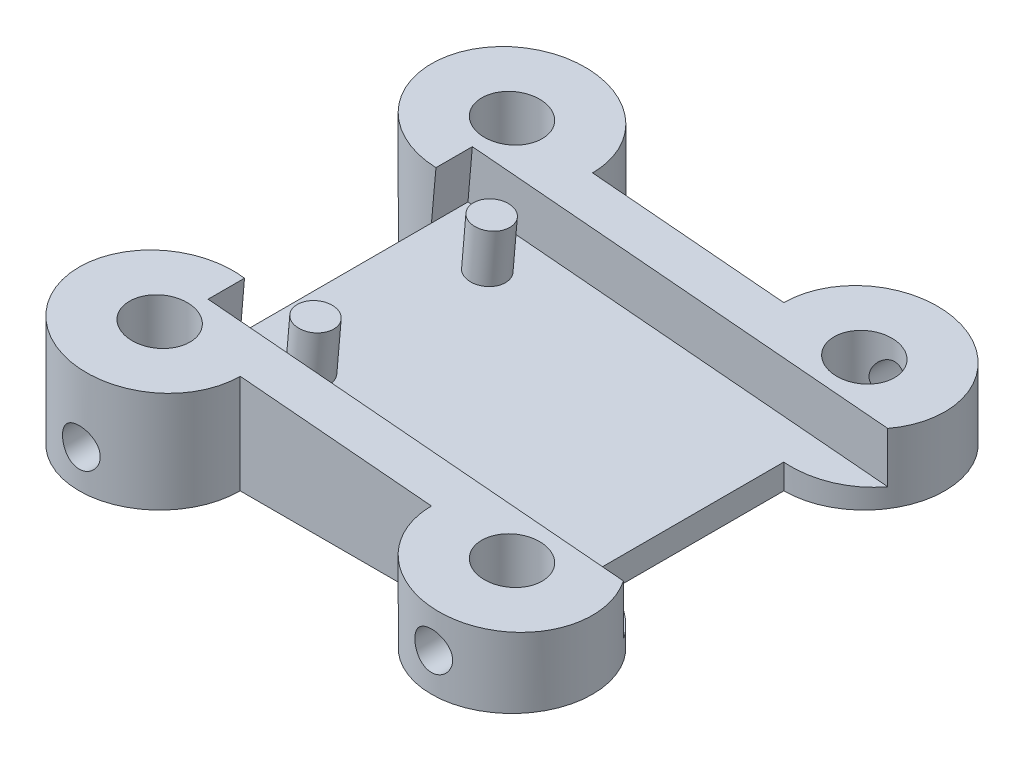
SolidWorks part; units mm, degrees
ref_plane "Front Plane" through (0, 0, 0) normal (0, 0, 1) x (1, 0, 0)
ref_plane "Top Plane" through (0, 0, 0) normal (0, 1, 0) x (1, 0, 0)
ref_plane "Right Plane" through (0, 0, 0) normal (1, 0, 0) x (0, 0, -1)
sketch "Sketch1" plane through (0, 0, 0) normal (0, 1, 0) x (1, 0, 0)
  line L0 (14, 28) -> (14, 0) construction
  line L1 (0, 0) -> (28, 0)
  line L2 (0, 0) -> (0, 28)
  line L3 (0, 28) -> (28, 28)
  line L4 (28, 0) -> (28, 28)
  line L5 (0, 14) -> (28, 14) construction
  point P9 (14, 14)
  dimension "D1" = 28
extrude "Boss-Extrude1" add sketch "Sketch1" along normal blind 8.4497
sketch "Sketch2" plane through (0, 0, 0) normal (0, 0, 1) x (1, 0, 0)
  line L0 (0, 8.4497) -> (28, 6)
  line L1 (0, 8.4497) -> (28, 8.4497) construction
  line L2 (28, 8.4497) -> (28, 0) construction
  line L3 (0, 8.4497) -> (28, 8.4497)
  line L4 (28, 8.4497) -> (28, 6)
  dimension "D2" = 6
  dimension "D3" = 5
extrude "Cut-Extrude1" cut sketch "Sketch2" against normal through all
sketch "Sketch3" plane through (0.7336, 8.3855, 0) normal (0.0872, 0.9962, 0) x (0.9962, -0.0872, 0)
  line L0 (-0.7364, 28) -> (-0.7364, 0) construction
  line L1 (-0.7364, 3.5) -> (49.2636, 3.5)
  line L2 (-0.7364, 3.5) -> (-0.7364, 24.5)
  line L3 (-0.7364, 24.5) -> (49.2636, 24.5)
  line L4 (49.2636, 3.5) -> (49.2636, 24.5)
  point P9 (-0.7364, 14)
  point P10 (-0.7364, 14)
  dimension "D1" = 21
  dimension "D2" = 50
extrude "Cut-Extrude2" cut sketch "Sketch3" against normal blind 4
ref_plane "Plane1" through (0, 8.4497, 0) normal (0, 1, 0) x (1, 0, 0)
sketch "Sketch11" plane through (0.385, 4.4007, 0) normal (0.0872, 0.9962, 0) x (0.9962, -0.0872, 0)
  line L0 (27.7205, 24.5) -> (-0.3865, 24.5) construction
  line L1 (27.7205, 24.5) -> (27.7205, 3.5) construction
  line L2 (-0.3865, 3.5) -> (27.7205, 3.5) construction
  line L3 (27.7205, 24.5) -> (-0.3865, 24.5) construction
  line L4 (27.7205, 24.5) -> (27.7205, 3.5) construction
  line L5 (-0.3865, 3.5) -> (27.7205, 3.5) construction
  line L6 (13.667, 3) -> (13.667, 50003) construction
  line L7 (24.633, 14) -> (-49975.367, 14) construction
  circle A2 centre (4.667, 21) radius 1.45
  circle A3 centre (4.667, 7) radius 1.45
  point P6 (13.667, 3.5)
  point P9 (27.7205, 14)
  dimension "D4" = 2.9
  dimension "D5" = 9
  dimension "D6" = 7
extrude "Boss-Extrude2" add sketch "Sketch11" along normal blind 4
sketch "Sketch12" plane through (0, 8.4497, 0) normal (0, 1, 0) x (1, 0, 0)
  line L0 (0, 3.5) -> (0, 24.5) construction
  line L1 (0, 3.5) -> (28, 3.5) construction
  line L2 (0, 3.5) -> (0, 24.5) construction
  line L3 (0, 3.5) -> (28, 3.5) construction
  line L4 (0, 14) -> (50000, 14) construction
  line L5 (14, 4) -> (14, 50004) construction
  circle A0 centre (14, 14) radius 7
  point P7 (0, 14)
  point P10 (14, 3.5)
  dimension "D1" = 14
sketch "Sketch13" plane through (0, 0, 0) normal (0, -1, 0) x (1, 0, 0)
  line L0 (0, 0) -> (28, 0) construction
  line L1 (28, 0) -> (28, -28) construction
  line L2 (28, -28) -> (0, -28) construction
  line L3 (0, -28) -> (0, 0) construction
  line L4 (0, 0) -> (28, 0) construction
  line L5 (28, 0) -> (28, -28) construction
  line L6 (28, -28) -> (0, -28) construction
  line L7 (0, -28) -> (0, 0) construction
  line L8 (0, -14) -> (28, -14) construction
  line L9 (14, -28) -> (14, 0) construction
  circle A0 centre (0, 0) radius 2.4
  circle A1 centre (28, 0) radius 2.4
  circle A2 centre (28, -28) radius 2.4
  circle A3 centre (0, -28) radius 2.4
  dimension "D1" = 4.8
  dimension "D2" = 2
  dimension "D3" = 2
extrude "Cut-Extrude5" cut sketch "Sketch13" against normal through all
sketch "Sketch14" plane through (0, 0, 0) normal (0, -1, 0) x (1, 0, 0)
  line L0 (28, -3.5) -> (28, -2.4) construction
  line L1 (2.4, -28) -> (25.6, -28) construction
  line L2 (0, -3.5) -> (0, -24.5) construction
  circle A0 centre (0, 0) radius 2.4 construction
  circle A1 centre (0, 0) radius 2.4 construction
  circle A2 centre (0, 0) radius 6.4
  circle A3 centre (0, 0) radius 2.4
  circle A4 centre (28, 0) radius 2.4
  circle A5 centre (28, 0) radius 6.4
  circle A6 centre (28, -28) radius 2.4
  circle A7 centre (28, -28) radius 6.4
  circle A8 centre (0, -28) radius 2.4
  circle A9 centre (0, -28) radius 6.4
  dimension "D1" = 4
  dimension "D4" = 4.8
  dimension "D2" = 2
  dimension "D3" = 2
extrude "Boss-Extrude3" add sketch "Sketch14" against normal up to surface (8.4497 mm away) up to face at (14, 7.2248, -25.8676)
sketch "Sketch15" plane through (0, 0, -28) normal (0, 0, -1) x (-1, 0, 0)
  line L0 (-21.6, 0) -> (-6.4, 0) construction
  line L1 (-21.9, 0) -> (-0.9, 0) construction
  line L4 (-14, 7.2248) -> (-14, 0) construction
  line L5 (-6.4, 7.8898) -> (-21.6, 6.5599) construction
  circle A0 centre (-28, 3) radius 1.5
  circle A1 centre (0, 3) radius 1.5
  point P4 (-28, 0)
  dimension "D1" = 3
  dimension "D2" = 3
extrude "Cut-Extrude6" cut sketch "Sketch15" along normal through all
sketch "Sketch16" plane through (0, 0, 0) normal (0, 0, 1) x (1, 0, 0)
  circle A0 centre (0, 3) radius 1.5 construction
  circle A1 centre (28, 3) radius 1.5 construction
  circle A2 centre (0, 3) radius 1.5
  circle A3 centre (28, 3) radius 1.5
extrude "Cut-Extrude7" cut sketch "Sketch16" along normal through all
sketch "Sketch18" plane through (0.7336, 8.3855, 0) normal (0.0872, 0.9962, 0) x (0.9962, -0.0872, 0)
  line L5 (-0.7364, 3.5) -> (27.157, 3.5) construction
  line L8 (4.6422, 3.5) -> (21.9919, 3.5) construction
  line L9 (4.6422, 3.5) -> (21.9919, 3.5) construction
  line L22 (4.9922, 24.5) -> (-0.3865, 24.5)
  line L37 (6.9919, 3.5) -> (36.9919, 3.5)
  line L38 (6.9919, 3.5) -> (6.9919, 24.5)
  line L39 (6.9919, 24.5) -> (36.9919, 24.5)
  line L40 (36.9919, 3.5) -> (36.9919, 24.5)
  line L42 (-0.3865, 24.5) -> (-0.3865, 21.6)
  line L46 (-0.3865, 6.4) -> (-0.3865, 3.5)
  line L47 (-0.3865, 3.5) -> (4.9922, 3.5)
  line L49 (4.6422, 24.5) -> (21.9919, 24.5) construction
  ellipse E1 centre (-0.3865, 28) end of major axis (6.038, 28) minor radius 6.4 (-0.3865, 21.6) -> (4.9922, 24.5) ccw construction
  ellipse E2 centre (-0.3865, 28) end of major axis (6.038, 28) minor radius 6.4 (-0.3865, 21.6) -> (4.9922, 24.5) ccw
  ellipse E3 centre (-0.3865, 0) end of major axis (6.038, 0) minor radius 6.4 (4.9922, 3.5) -> (-0.3865, 6.4) ccw construction
  ellipse E4 centre (-0.3865, 0) end of major axis (6.038, 0) minor radius 6.4 (4.9922, 3.5) -> (-0.3865, 6.4) ccw
  point P7 (21.9919, 3.5)
  dimension "D1" = 30
extrude "Cut-Extrude8" cut sketch "Sketch18" against normal up to surface (4 mm away) up to face at (6.4787, 3.8676, -21)
equation "\"TrackLength\"= 150"
equation "\"MarbleWidth\"= 13"
equation "\"MarbleTrackWidth\"= \"MarbleWidth\" - 1"
equation "\"TrackWidth\"= \"MarbleTrackWidth\" + ( 2 * 4 )"
equation "\"MarbleTrackLength\"= \"TrackLength\" - ( 2 * 8 )"
equation "\"MountWidth\"= \"TrackWidth\" + 8"
equation "\"D1@Sketch1\"=\"MountWidth\""
equation "\"D1@Boss-Extrude1\"=\"RampHeight\""
equation "\"RampDepth\"=6"
equation "\"RampAngle\"= 5"
equation "\"RampHeight\"= ( \"MountWidth\" * tan ( \"RampAngle\" ) ) + \"RampDepth\""
equation "\"D1@Sketch3\"=\"TrackWidth\" + 1"
equation "\"MountWidth\"= \"TrackWidth\" + 10"
equation "\"MountLength\"=66.6651"
